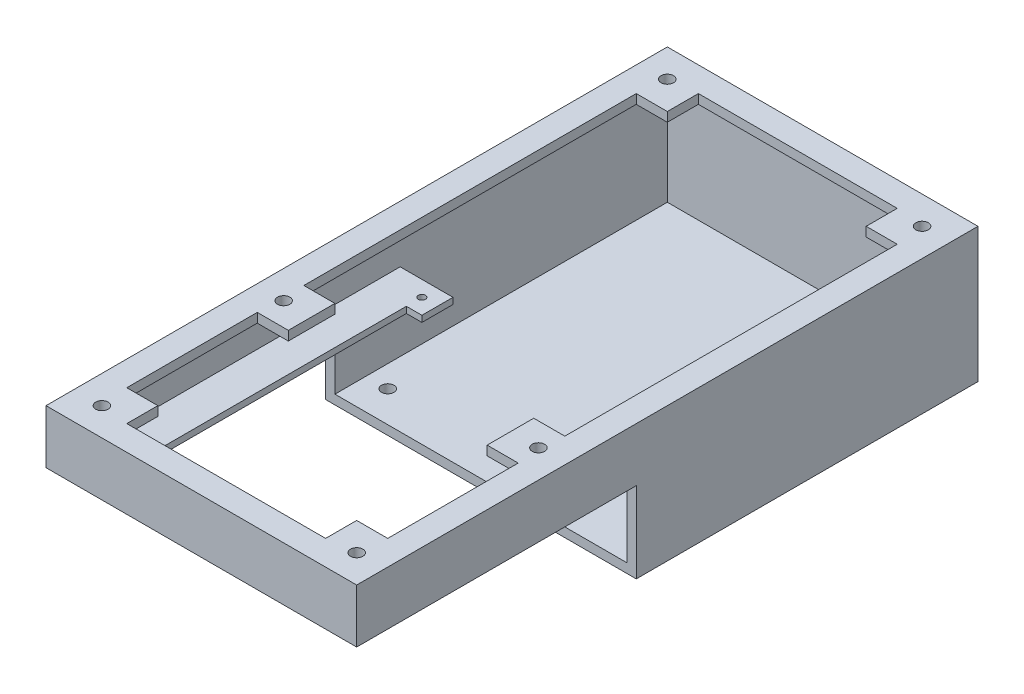
SolidWorks part; units mm, degrees
ref_plane "Front Plane" through (0, 0, 0) normal (0, 0, 1) x (1, 0, 0)
ref_plane "Top Plane" through (0, 0, 0) normal (0, 1, 0) x (1, 0, 0)
ref_plane "Right Plane" through (0, 0, 0) normal (1, 0, 0) x (0, 0, -1)
sketch "Sketch1" plane through (0, 0, 0) normal (0, 1, 0) x (1, 0, 0)
  line L1 (-50, 100) -> (50, 100)
  line L2 (-50, 100) -> (-50, -100)
  line L3 (-50, -100) -> (50, -100)
  line L4 (50, 100) -> (50, -100)
  line L5 (-50, 100) -> (50, -100) construction
  line L6 (-50, -100) -> (50, 100) construction
  line L7 (-33.5, 90) -> (33.5, 90)
  line L8 (-33.5, 90) -> (-33.5, -20)
  line L9 (-33.5, -20) -> (33.5, -20)
  line L10 (33.5, 90) -> (33.5, -20)
  line L11 (-33.5, 90) -> (33.5, -20) construction
  line L12 (-33.5, -20) -> (33.5, 90) construction
  point P0 (0, 0)
  dimension "D1" = 100
  dimension "D2" = 200
  dimension "D3" = 67
  dimension "D4" = 110
  dimension "D5" = 10
extrude "Boss-Extrude1" add sketch "Sketch1" along normal blind 2
sketch "Sketch2" plane through (0, 0, 0) normal (0, -1, 0) x (1, 0, 0)
  line L0 (-50, 100) -> (50, 100)
  line L1 (50, 100) -> (50, -100)
  line L2 (50, -100) -> (-50, -100)
  line L3 (-50, -100) -> (-50, 100)
  line L5 (-47, 97) -> (47, 97)
  line L6 (-47, 97) -> (-47, -97)
  line L7 (-47, -97) -> (47, -97)
  line L8 (47, 97) -> (47, -97)
  dimension "D1" = 3
  dimension "D2" = 3
  dimension "D3" = 3
  dimension "D4" = 3
extrude "Boss-Extrude2" add sketch "Sketch2" along normal blind 16.4
sketch "Sketch3" plane through (0, -16.4, 0) normal (0, -1, 0) x (1, 0, 0)
  line L0 (-50, 100) -> (50, 100)
  line L1 (50, -100) -> (50, 100) construction
  line L2 (50, 100) -> (-50, 100) construction
  line L3 (50, 100) -> (50, 10)
  line L4 (-50, 100) -> (-50, 10)
  line L5 (-50, 100) -> (-50, -100) construction
  line L6 (-35, 80) -> (35, 80)
  line L7 (35, 80) -> (35, 10)
  line L9 (-35, 80) -> (-35, 10)
  line L11 (-50, -11) -> (-30, -11)
  line L12 (50, -11) -> (50, 10)
  line L13 (-50, -11) -> (-50, 10)
  line L14 (-35, 10) -> (-35, -1)
  line L15 (35, 10) -> (35, -1)
  line L16 (35, -1) -> (30, -1)
  line L17 (-30, -1) -> (-30, -11)
  line L18 (30, -1) -> (30, -11)
  line L19 (-30, -1) -> (-35, -1)
  line L20 (30, -11) -> (50, -11)
  circle A0 centre (-35, 85) radius 1.15
  circle A1 centre (35, 85) radius 1.15
  circle A2 centre (-35, -6) radius 1.15
  circle A3 centre (35, -6) radius 1.15
  dimension "D1" = 2.3
  dimension "D2" = 2.3
  dimension "D12" = 2.3
  dimension "D15" = 2.3
  dimension "D3" = 15
  dimension "D4" = 15
  dimension "D5" = 15
  dimension "D6" = 15
  dimension "D7" = 15
  dimension "D8" = 15
  dimension "D9" = 20
  dimension "D10" = 5
  dimension "D11" = 5
  dimension "D13" = 0
  dimension "D14" = 91
  dimension "D16" = 70
  dimension "D17" = 5
  dimension "D18" = 5
extrude "Boss-Extrude3" add sketch "Sketch3" along normal blind 2
sketch "Sketch5" plane through (0, -16.4, 0) normal (0, -1, 0) x (1, 0, 0)
  line L0 (-50, -100) -> (50, -100)
  line L1 (50, -100) -> (50, -97)
  line L2 (50, -100) -> (50, -11) construction
  line L3 (47, -97) -> (-47, -97)
  line L4 (-50, -11) -> (-50, -100) construction
  line L5 (-50, -97) -> (-50, -100)
  line L6 (-50, -97) -> (-50, 10)
  line L7 (-50, 10) -> (-47, 10)
  line L8 (-47, -11) -> (-47, -97) construction
  line L9 (-47, 10) -> (-47, -97)
  line L10 (50, -97) -> (50, 10)
  line L11 (50, 10) -> (47, 10)
  line L12 (47, -97) -> (47, -11) construction
  line L13 (47, 10) -> (47, -97)
  dimension "D1" = 3
  dimension "D2" = 110
  dimension "D3" = 110
extrude "Boss-Extrude4" add sketch "Sketch5" along normal blind 25
sketch "Sketch8" plane through (0, -41.4, 0) normal (0, -1, 0) x (1, 0, 0)
  line L1 (-50, 10) -> (50, 10)
  line L2 (-50, 10) -> (-50, -100)
  line L3 (-50, -100) -> (50, -100)
  line L4 (50, 10) -> (50, -100)
extrude "Boss-Extrude5" add sketch "Sketch8" along normal blind 3
sketch "Sketch9" plane through (0, -16.4, 0) normal (0, 1, 0) x (1, 0, 0)
  line L0 (-35, 6) -> (-35, -85) construction
  line L2 (-34.15, -68) -> (-23.15, -68)
  line L3 (-34.15, -68) -> (-34.15, -81)
  line L4 (-34.15, -81) -> (-23.15, -81)
  line L5 (-23.15, -68) -> (-23.15, -81)
  line L6 (-34.15, -68) -> (-23.15, -81) construction
  line L7 (-34.15, -81) -> (-23.15, -68) construction
  line L8 (-6.21, -68) -> (4.79, -68)
  line L9 (-6.21, -68) -> (-6.21, -81)
  line L10 (-6.21, -81) -> (4.79, -81)
  line L11 (4.79, -68) -> (4.79, -81)
  line L12 (-6.21, -68) -> (4.79, -81) construction
  line L13 (-6.21, -81) -> (4.79, -68) construction
  line L14 (19.19, -68) -> (30.19, -68)
  line L15 (19.19, -68) -> (19.19, -81)
  line L16 (19.19, -81) -> (30.19, -81)
  line L17 (30.19, -68) -> (30.19, -81)
  line L18 (19.19, -68) -> (30.19, -81) construction
  line L19 (19.19, -81) -> (30.19, -68) construction
  line L20 (-34.15, -42.6) -> (-23.15, -42.6)
  line L21 (-34.15, -42.6) -> (-34.15, -55.6)
  line L22 (-34.15, -55.6) -> (-23.15, -55.6)
  line L23 (-23.15, -42.6) -> (-23.15, -55.6)
  line L24 (-34.15, -42.6) -> (-23.15, -55.6) construction
  line L25 (-34.15, -55.6) -> (-23.15, -42.6) construction
  line L26 (-6.21, -42.6) -> (4.79, -42.6)
  line L27 (-6.21, -42.6) -> (-6.21, -55.6)
  line L28 (-6.21, -55.6) -> (4.79, -55.6)
  line L29 (4.79, -42.6) -> (4.79, -55.6)
  line L30 (-6.21, -42.6) -> (4.79, -55.6) construction
  line L31 (-6.21, -55.6) -> (4.79, -42.6) construction
  line L32 (19.19, -42.6) -> (30.19, -42.6)
  line L33 (19.19, -42.6) -> (19.19, -55.6)
  line L34 (19.19, -55.6) -> (30.19, -55.6)
  line L35 (30.19, -42.6) -> (30.19, -55.6)
  line L36 (19.19, -42.6) -> (30.19, -55.6) construction
  line L37 (19.19, -55.6) -> (30.19, -42.6) construction
  point P4 (-28.65, -74.5)
  point P9 (-0.71, -74.5)
  point P14 (24.69, -74.5)
  point P19 (-28.65, -49.1)
  point P24 (-0.71, -49.1)
  point P29 (24.69, -49.1)
  dimension "D1" = 91
  dimension "D2" = 13
  dimension "D3" = 11
  dimension "D4" = 13
  dimension "D5" = 11
  dimension "D6" = 11
  dimension "D7" = 11
  dimension "D8" = 11
  dimension "D9" = 11
  dimension "D10" = 13
  dimension "D11" = 13
  dimension "D12" = 13
  dimension "D13" = 13
  dimension "D14" = 10.5
  dimension "D15" = 6.35
  dimension "D16" = 27.94
  dimension "D17" = 25.4
  dimension "D18" = 10.5
  dimension "D19" = 10.5
  dimension "D20" = 6.35
  dimension "D21" = 27.94
  dimension "D22" = 25.4
  dimension "D23" = 25.4
  dimension "D24" = 25.4
extrude "Cut-Extrude2" cut sketch "Sketch9" along normal blind 36
sketch "Sketch13" plane through (0, 2, 0) normal (0, 1, 0) x (1, 0, 0)
  line L1 (-63.1803, 106.247) -> (78.3246, 106.247)
  line L2 (-63.1803, 106.247) -> (-63.1803, -106.7202)
  line L3 (-63.1803, -106.7202) -> (78.3246, -106.7202)
  line L4 (78.3246, 106.247) -> (78.3246, -106.7202)
extrude "Cut-Extrude6" cut sketch "Sketch13" against normal blind 3.1
sketch "Sketch14" plane through (0, -1.1, 0) normal (0, 1, 0) x (1, 0, 0)
  line L1 (-47, 97) -> (47, 97)
  line L2 (-47, 97) -> (-47, -97)
  line L3 (-47, -97) -> (47, -97)
  line L4 (47, 97) -> (47, -97)
  line L5 (-32, 92) -> (32, 92)
  line L6 (-42, 82) -> (-42, -25)
  line L7 (-32, -92) -> (32, -92)
  line L8 (42, 82) -> (42, -25)
  line L9 (-47, -97) -> (-32, -97)
  line L10 (-47, -97) -> (-47, -82)
  line L11 (-42, -82) -> (-32, -82)
  line L12 (-32, -92) -> (-32, -82)
  line L13 (47, -97) -> (32, -97)
  line L14 (47, -97) -> (47, -82)
  line L15 (42, -82) -> (32, -82)
  line L16 (32, -92) -> (32, -82)
  line L17 (47, 97) -> (32, 97)
  line L18 (47, 97) -> (47, 82)
  line L19 (42, 82) -> (32, 82)
  line L20 (32, 92) -> (32, 82)
  line L21 (-47, 97) -> (-32, 97)
  line L22 (-47, 97) -> (-47, 82)
  line L23 (-42, 82) -> (-32, 82)
  line L24 (-32, 92) -> (-32, 82)
  line L25 (42, -25) -> (32, -25)
  line L26 (47, -25) -> (47, -40)
  line L27 (42, -40) -> (32, -40)
  line L28 (32, -25) -> (32, -40)
  line L29 (-42, -25) -> (-32, -25)
  line L30 (-47, -25) -> (-47, -40)
  line L31 (-42, -40) -> (-32, -40)
  line L32 (-32, -25) -> (-32, -40)
  line L33 (-42, -40) -> (-42, -82)
  line L34 (42, -40) -> (42, -82)
  point P38 (0, 0)
  point P39 (0, 0)
  dimension "D1" = 5
  dimension "D2" = 5
  dimension "D3" = 5
  dimension "D4" = 5
  dimension "D5" = 15
  dimension "D6" = 15
  dimension "D7" = 15
  dimension "D8" = 15
  dimension "D9" = 15
  dimension "D10" = 15
  dimension "D11" = 15
  dimension "D12" = 15
  dimension "D13" = 57
  dimension "D14" = 57
  dimension "D15" = 15
  dimension "D16" = 15
  dimension "D17" = 15
  dimension "D18" = 15
extrude "Boss-Extrude6" add sketch "Sketch14" against normal blind 3 contours L2 L1 L4 L3
extrude "Cut-Extrude7" cut sketch "Sketch14<4>" against normal blind 3 contours L5 L20 L19 L8 L25 L28 L27 L34 L15 L16 L7 L12 L11 L33 L31 L32 L29 L6 L23 L24
sketch "Sketch14<4>" plane through (0, -1.1, 0) normal (0, 1, 0) x (1, 0, 0) same geometry as "Sketch14"
sketch "Sketch15" plane through (0, -44.4, 0) normal (0, -1, 0) x (1, 0, 0)
  line L0 (-50, 10) -> (-50, -100) construction
  line L1 (50, 10) -> (-50, 10) construction
  line L2 (50, -100) -> (50, 10) construction
  circle A0 centre (-40, 0) radius 2
  circle A1 centre (40, 0) radius 2
  dimension "D1" = 4
  dimension "D2" = 4
  dimension "D3" = 10
  dimension "D4" = 10
  dimension "D5" = 10
  dimension "D6" = 10
extrude "Cut-Extrude8" cut sketch "Sketch15" against normal blind 3
sketch "Sketch16" plane through (0, -18.4, 0) normal (0, -1, 0) x (1, 0, 0)
  line L0 (-50, 100) -> (-50, 10) construction
  line L1 (50, 100) -> (-50, 100) construction
  line L2 (50, 10) -> (50, 100) construction
  circle A0 centre (-40, 92.5) radius 2
  circle A1 centre (40, 92.5) radius 2
  point P6 (0, 0)
  point P8 (-38.0193, 99.4241)
  dimension "D1" = 4
  dimension "D2" = 4
  dimension "D6" = 10
  dimension "D3" = 10
  dimension "D4" = 7.5
  dimension "D5" = 7.5
extrude "Cut-Extrude9" cut sketch "Sketch16" against normal blind 3
sketch "Sketch17" plane through (0, -1.1, 0) normal (0, 1, 0) x (1, 0, 0)
  line L0 (50, 100) -> (-50, 100) construction
  line L2 (-50, 100) -> (-50, -100) construction
  line L3 (50, -100) -> (50, 100) construction
  line L4 (-42, -40) -> (-32, -40) construction
  line L5 (42, -40) -> (32, -40) construction
  line L6 (-50, -100) -> (50, -100) construction
  circle A0 centre (-41, 91) radius 2
  circle A1 centre (41, 91) radius 2
  circle A2 centre (-41, -32.5) radius 2
  circle A3 centre (41, -32.5) radius 2
  circle A4 centre (-41, -91) radius 2
  circle A5 centre (41, -91) radius 2
  dimension "D1" = 4
  dimension "D2" = 9
  dimension "D3" = 9
  dimension "D4" = 4
  dimension "D5" = 9
  dimension "D6" = 9
  dimension "D7" = 4
  dimension "D8" = 4
  dimension "D9" = 4
  dimension "D10" = 4
  dimension "D11" = 9
  dimension "D12" = 9
  dimension "D13" = 7.5
  dimension "D14" = 7.5
  dimension "D15" = 9
  dimension "D16" = 9
  dimension "D17" = 9
  dimension "D18" = 9
extrude "Cut-Extrude10" cut sketch "Sketch17" against normal blind 3
